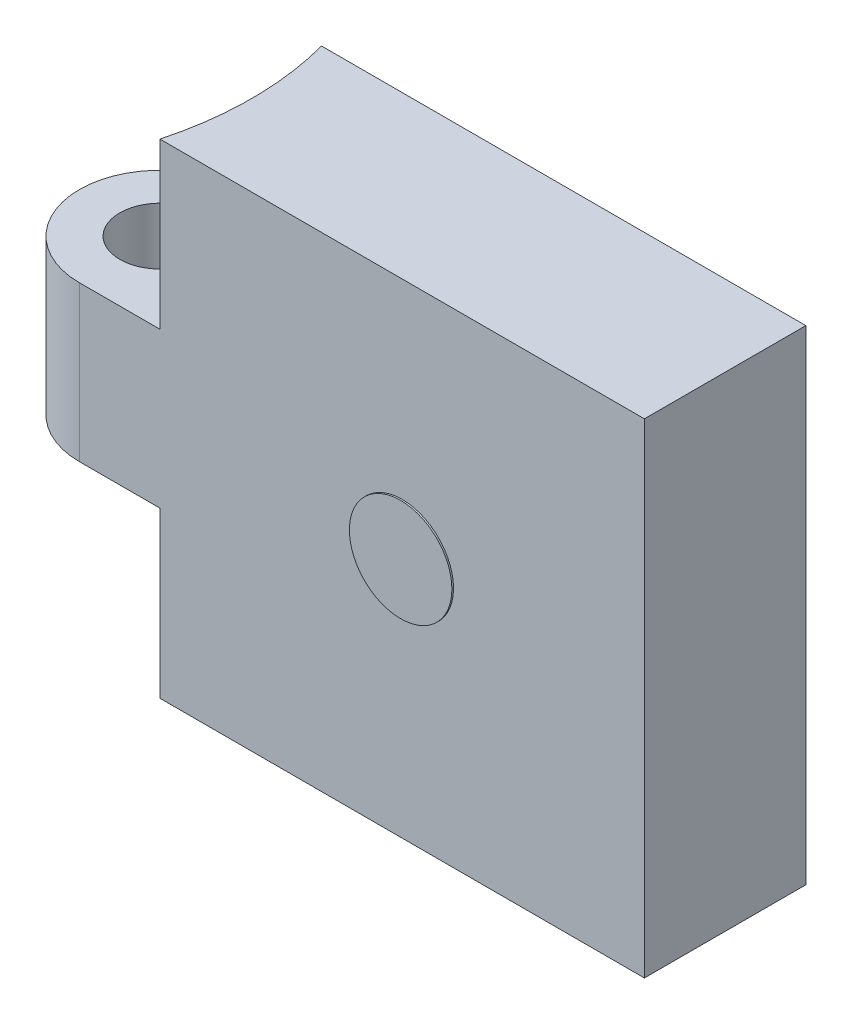
SolidWorks part; units mm, degrees
ref_plane "Plano frontal" through (0, 0, 0) normal (0, 0, 1) x (1, 0, 0)
ref_plane "Plano superior" through (0, 0, 0) normal (0, 1, 0) x (1, 0, 0)
ref_plane "Plano direito" through (0, 0, 0) normal (1, 0, 0) x (0, 0, -1)
sketch "Esboço1" plane through (0, 0, 0) normal (0, 0, 1) x (1, 0, 0)
  line L0 (20, 15) -> (-20, -15) construction
  line L1 (-10, 15) -> (20, 15)
  line L2 (-20, 4.8) -> (-20, -4.8)
  line L3 (-10, -15) -> (20, -15)
  line L4 (20, 15) -> (20, -15)
  line L5 (-10, 15) -> (-10, 4.8)
  line L6 (-20, 4.8) -> (-10, 4.8)
  line L7 (-20, 4.8) -> (-20, -4.8)
  line L8 (-20, -4.8) -> (-10, -4.8)
  line L10 (-10, -4.8) -> (-10, -15)
  dimension "D2" = 40
  dimension "D3" = 10.2
  dimension "D4" = 10.2
  dimension "D5" = 10
extrude "Ressalto-extrusão1" add sketch "Esboço1" along normal blind 10 contours L0 L1 L5 L6 L2 L8 L10 | L4 L0 L10 L3 region at (8, -4.5, 0) region at (-3.3218, 5.8391, 0)
sketch "Esboço2" plane through (0, -4.8, 0) normal (0, -1, 0) x (1, 0, 0)
  circle A0 centre (-15, 5) radius 2.5
  dimension "D1" = 5
extrude "Corte-extrusão1" cut sketch "Esboço2" against normal blind 10
fillet "Filete1" radius 5 2 edges at (-20, 0, 0) (-20, 0, 10)
sketch "Esboço5" plane through (0, -15, 0) normal (0, -1, 0) x (1, 0, 0)
  line L0 (-10, 10) -> (-10, 0)
  arc A0 (-10, 10) -> (-10, 0) centre (-28.6603, 5) cw
extrude "Corte-extrusão4" cut sketch "Esboço5" against normal blind 10
sketch "Esboço6" plane through (0, 15, 0) normal (0, 1, 0) x (1, 0, 0)
  line L0 (-10, -10) -> (-10, 0) construction
  line L1 (-10, -9.9505) -> (-10, 0)
  arc A0 (-10, 0) -> (-10, -9.9505) centre (-28.568, -4.9753) cw
extrude "Corte-extrusão5" cut sketch "Esboço6" against normal blind 10
sketch "Esboço7" plane through (0, 0, 10) normal (0, 0, 1) x (1, 0, 0)
  line L0 (-10, -15) -> (20, 15) construction
  line L1 (20, -15) -> (5, 0) construction
  circle A0 centre (5, 0) radius 3.175
  dimension "D1" = 6.35
extrude "Ressalto-extrusão2" add sketch "Esboço7" along normal blind 0.1
